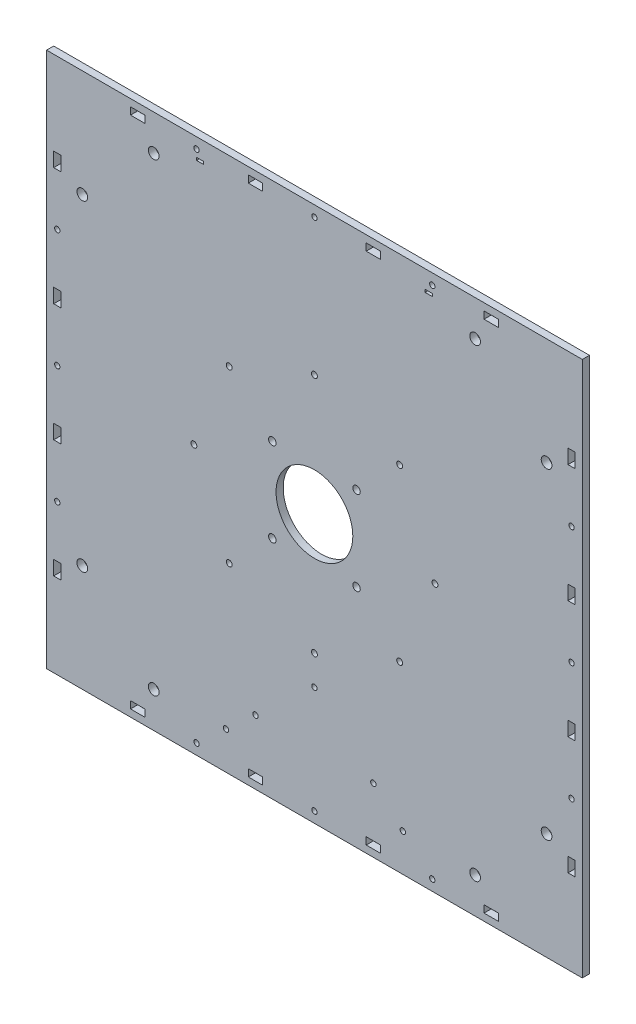
SolidWorks part; units mm, degrees
ref_plane "前视基准面" through (0, 0, 0) normal (0, 0, 1) x (1, 0, 0)
ref_plane "上视基准面" through (0, 0, 0) normal (0, 1, 0) x (1, 0, 0)
ref_plane "右视基准面" through (0, 0, 0) normal (1, 0, 0) x (0, 0, -1)
sketch "草图1" plane through (0, 0, 0) normal (0, 0, 1) x (1, 0, 0)
  line L0 (1.4571, -21.1871) -> (1.4571, -41.1871) construction
  line L1 (63.4571, 98.8129) -> (67.4571, 98.8129)
  line L2 (1.4571, -21.1871) -> (1.4571, 44.8129) construction
  line L3 (67.4571, 98.8129) -> (67.4571, 97.3129)
  line L4 (151.4571, -41.1871) -> (151.4571, 108.8129)
  line L5 (151.4571, 108.8129) -> (-148.5429, 108.8129)
  line L6 (-148.5429, 108.8129) -> (-148.5429, -191.1871)
  line L7 (-148.5429, -191.1871) -> (151.4571, -191.1871)
  line L8 (151.4571, -191.1871) -> (151.4571, -41.1871)
  line L9 (-148.5429, -41.1871) -> (-161.9412, -41.1871) construction
  line L10 (1.4571, -191.1871) -> (1.4571, -181.0361) construction
  line L11 (67.4571, 97.3129) -> (63.4571, 97.3129)
  line L12 (63.4571, 97.3129) -> (63.4571, 98.8129)
  line L13 (-64.5429, 98.8129) -> (-64.5429, 97.3129)
  line L14 (-64.5429, 97.3129) -> (-60.5429, 97.3129)
  line L15 (-60.5429, 97.3129) -> (-60.5429, 98.8129)
  line L16 (-60.5429, 98.8129) -> (-64.5429, 98.8129)
  circle A6 centre (1.4571, -21.1871) radius 241.4173 construction
  circle A9 centre (1.4571, -41.1871) radius 21.5
  circle A10 centre (25.0271, -17.6171) radius 2.1
  circle A11 centre (25.0271, -64.7571) radius 2.1
  circle A12 centre (-22.1129, -64.7571) radius 2.1
  circle A13 centre (-22.1129, -17.6171) radius 2.1
  dimension "D1" = 43
  dimension "D4" = 4.2
  dimension "D2" = 300
  dimension "D3" = 300
  dimension "D5" = 23.57
  dimension "D6" = 23.57
  dimension "D7" = 4
extrude "凸台-拉伸1" add sketch "草图1" along normal blind 4
sketch "草图3" plane through (0, 0, 4) normal (0, 0, 1) x (1, 0, 0)
  line L1 (96.4421, -183.1721) -> (104.4721, -183.1721)
  line L13 (1.4571, -191.1871) -> (1.4571, -185.1871) construction
  line L14 (-148.5429, -191.1871) -> (151.4571, -191.1871) construction
  line L15 (1.4571, -185.1871) -> (34.4571, -185.1871) construction
  line L16 (34.4571, -185.1871) -> (67.4571, -185.1871) construction
  line L17 (30.4421, -183.1721) -> (38.4721, -183.1721)
  line L18 (30.4421, -183.1721) -> (30.4421, -187.2021)
  line L19 (30.4421, -187.2021) -> (38.4721, -187.2021)
  line L20 (38.4721, -183.1721) -> (38.4721, -187.2021)
  line L21 (30.4421, -183.1721) -> (38.4721, -187.2021) construction
  line L22 (30.4421, -187.2021) -> (38.4721, -183.1721) construction
  line L23 (67.4571, -185.1871) -> (100.4571, -185.1871) construction
  line L24 (96.4421, -183.1721) -> (96.4421, -187.2021)
  line L25 (96.4421, -187.2021) -> (104.4721, -187.2021)
  line L26 (96.4421, -187.2021) -> (104.4721, -183.1721) construction
  line L27 (104.4721, -187.2021) -> (104.4721, -183.1721)
  line L28 (-35.5579, -183.1721) -> (-35.5579, -187.2021)
  line L29 (-27.5279, -183.1721) -> (-35.5579, -183.1721)
  line L30 (-27.5279, -183.1721) -> (-27.5279, -187.2021)
  line L31 (-27.5279, -187.2021) -> (-35.5579, -187.2021)
  line L32 (-93.5279, -183.1721) -> (-93.5279, -187.2021)
  line L33 (-101.5579, -187.2021) -> (-101.5579, -183.1721)
  line L34 (-93.5279, -183.1721) -> (-101.5579, -183.1721)
  line L35 (-93.5279, -187.2021) -> (-101.5579, -187.2021)
  line L36 (-140.5279, 53.7979) -> (-140.5279, 61.8279)
  line L37 (-144.5579, 53.7979) -> (-144.5579, 61.8279)
  line L38 (-144.5579, 61.8279) -> (-140.5279, 61.8279)
  line L39 (-140.5279, 53.7979) -> (-144.5579, 53.7979)
  line L40 (-140.5279, -12.2021) -> (-140.5279, -4.1721)
  line L41 (-140.5279, -4.1721) -> (-144.5579, -4.1721)
  line L42 (-144.5579, -12.2021) -> (-144.5579, -4.1721)
  line L43 (-140.5279, -12.2021) -> (-144.5579, -12.2021)
  line L44 (-140.5279, -70.1721) -> (-144.5579, -70.1721)
  line L45 (-140.5279, -70.1721) -> (-140.5279, -78.2021)
  line L46 (-144.5579, -70.1721) -> (-144.5579, -78.2021)
  line L47 (-140.5279, -78.2021) -> (-144.5579, -78.2021)
  line L48 (-140.5279, -136.1721) -> (-140.5279, -144.2021)
  line L49 (-144.5579, -136.1721) -> (-144.5579, -144.2021)
  line L50 (-140.5279, -136.1721) -> (-144.5579, -136.1721)
  line L51 (-144.5579, -144.2021) -> (-140.5279, -144.2021)
  line L52 (96.4421, 100.7979) -> (104.4721, 100.7979)
  line L53 (96.4421, 104.8279) -> (104.4721, 104.8279)
  line L54 (104.4721, 104.8279) -> (104.4721, 100.7979)
  line L55 (96.4421, 100.7979) -> (96.4421, 104.8279)
  line L56 (30.4421, 100.7979) -> (38.4721, 100.7979)
  line L57 (38.4721, 100.7979) -> (38.4721, 104.8279)
  line L58 (30.4421, 104.8279) -> (38.4721, 104.8279)
  line L59 (30.4421, 100.7979) -> (30.4421, 104.8279)
  line L60 (-27.5279, 100.7979) -> (-27.5279, 104.8279)
  line L61 (-27.5279, 100.7979) -> (-35.5579, 100.7979)
  line L62 (-27.5279, 104.8279) -> (-35.5579, 104.8279)
  line L63 (-35.5579, 100.7979) -> (-35.5579, 104.8279)
  line L64 (-93.5279, 100.7979) -> (-101.5579, 100.7979)
  line L65 (-93.5279, 104.8279) -> (-101.5579, 104.8279)
  line L66 (-93.5279, 100.7979) -> (-93.5279, 104.8279)
  line L67 (-101.5579, 104.8279) -> (-101.5579, 100.7979)
  line L68 (143.4421, -136.1721) -> (143.4421, -144.2021)
  line L69 (147.4721, -136.1721) -> (147.4721, -144.2021)
  line L70 (147.4721, -144.2021) -> (143.4421, -144.2021)
  line L71 (143.4421, -136.1721) -> (147.4721, -136.1721)
  line L72 (143.4421, -70.1721) -> (143.4421, -78.2021)
  line L73 (143.4421, -78.2021) -> (147.4721, -78.2021)
  line L74 (147.4721, -70.1721) -> (147.4721, -78.2021)
  line L75 (143.4421, -70.1721) -> (147.4721, -70.1721)
  line L76 (143.4421, -12.2021) -> (147.4721, -12.2021)
  line L77 (143.4421, -12.2021) -> (143.4421, -4.1721)
  line L78 (147.4721, -12.2021) -> (147.4721, -4.1721)
  line L79 (143.4421, -4.1721) -> (147.4721, -4.1721)
  line L80 (143.4421, 53.7979) -> (143.4421, 61.8279)
  line L81 (147.4721, 53.7979) -> (147.4721, 61.8279)
  line L82 (143.4421, 53.7979) -> (147.4721, 53.7979)
  line L83 (147.4721, 61.8279) -> (143.4421, 61.8279)
  line L84 (50.9571, -185.1871) -> (50.9571, -170.1871) construction
  line L85 (17.9571, -185.1871) -> (17.9571, -170.1871) construction
  line L86 (-48.0429, -170.1871) -> (-15.0429, -170.1871) construction
  line L91 (-31.5429, -170.1871) -> (-31.5429, -155.1871) construction
  circle A0 centre (1.4571, -185.1871) radius 1.5
  circle A1 centre (67.4571, -185.1871) radius 1.5
  circle A2 centre (-64.5429, -185.1871) radius 1.5
  circle A3 centre (-142.5429, 24.8129) radius 1.5
  circle A4 centre (-142.5429, -41.1871) radius 1.5
  circle A5 centre (-142.5429, -107.1871) radius 1.5
  circle A6 centre (67.4571, 102.8129) radius 1.5
  circle A7 centre (1.4571, 102.8129) radius 1.5
  circle A8 centre (-64.5429, 102.8129) radius 1.5
  circle A9 centre (145.4571, -107.1871) radius 1.5
  circle A10 centre (145.4571, -41.1871) radius 1.5
  circle A11 centre (145.4571, 24.8129) radius 1.5
  circle A15 centre (17.9571, -170.1871) radius 2 construction
  circle A16 centre (-15.0429, -170.1871) radius 2 construction
  circle A17 centre (50.9571, -170.1871) radius 1.5
  circle A18 centre (-48.0429, -170.1871) radius 1.5
  circle A19 centre (-31.5429, -155.1871) radius 1.5
  circle A20 centre (34.4571, -155.1871) radius 1.5
  circle A22 centre (1.4571, -155.1871) radius 2 construction
  circle A23 centre (1.4571, -41.1871) radius 67.5 construction
  circle A24 centre (1.4571, -108.6871) radius 1.65
  circle A25 centre (-46.2726, -88.9169) radius 1.65
  circle A26 centre (-66.0429, -41.1871) radius 1.65
  circle A27 centre (-46.2726, 6.5426) radius 1.65
  circle A28 centre (1.4571, 26.3129) radius 1.65
  circle A29 centre (49.1869, 6.5426) radius 1.65
  circle A30 centre (68.9571, -41.1871) radius 1.65
  circle A31 centre (49.1869, -88.9169) radius 1.65
  circle A32 centre (1.4571, -125.1871) radius 1.5
  dimension "D1" = 8.03
  dimension "D3" = 4
  dimension "D4" = 8
  dimension "D5" = 30
  dimension "D6" = 3.3
  dimension "D2" = 4.03
extrude "切除-拉伸2" cut sketch "草图3" against normal blind 4
sketch "草图6" plane through (0, 0, 4) normal (0, 0, 1) x (1, 0, 0)
sketch "草图7" plane through (0, 0, 4) normal (0, 0, 1) x (1, 0, 0)
  line L5 (-148.5429, -171.1871) -> (151.4571, -171.1871) construction
  line L6 (-148.5429, 108.8129) -> (-148.5429, -191.1871) construction
  line L7 (151.4571, -191.1871) -> (151.4571, 108.8129) construction
  line L8 (-148.5429, -191.1871) -> (151.4571, -191.1871) construction
  circle A0 centre (-88.5429, -171.1871) radius 3
  circle A1 centre (91.4571, -171.1871) radius 3
  circle A2 centre (-128.5429, 48.8129) radius 3
  circle A3 centre (-128.5429, -131.1871) radius 3
  circle A4 centre (91.4571, 88.8129) radius 3
  circle A5 centre (-88.5429, 88.8129) radius 3
  circle A6 centre (131.4571, -131.1871) radius 3
  circle A7 centre (131.4571, 48.8129) radius 3
  dimension "D2" = 6
  dimension "D4" = 60
  dimension "D1" = 20
  dimension "D3" = 60
  dimension "D5" = 4
extrude "切除-拉伸3" cut sketch "草图7" against normal blind 10
